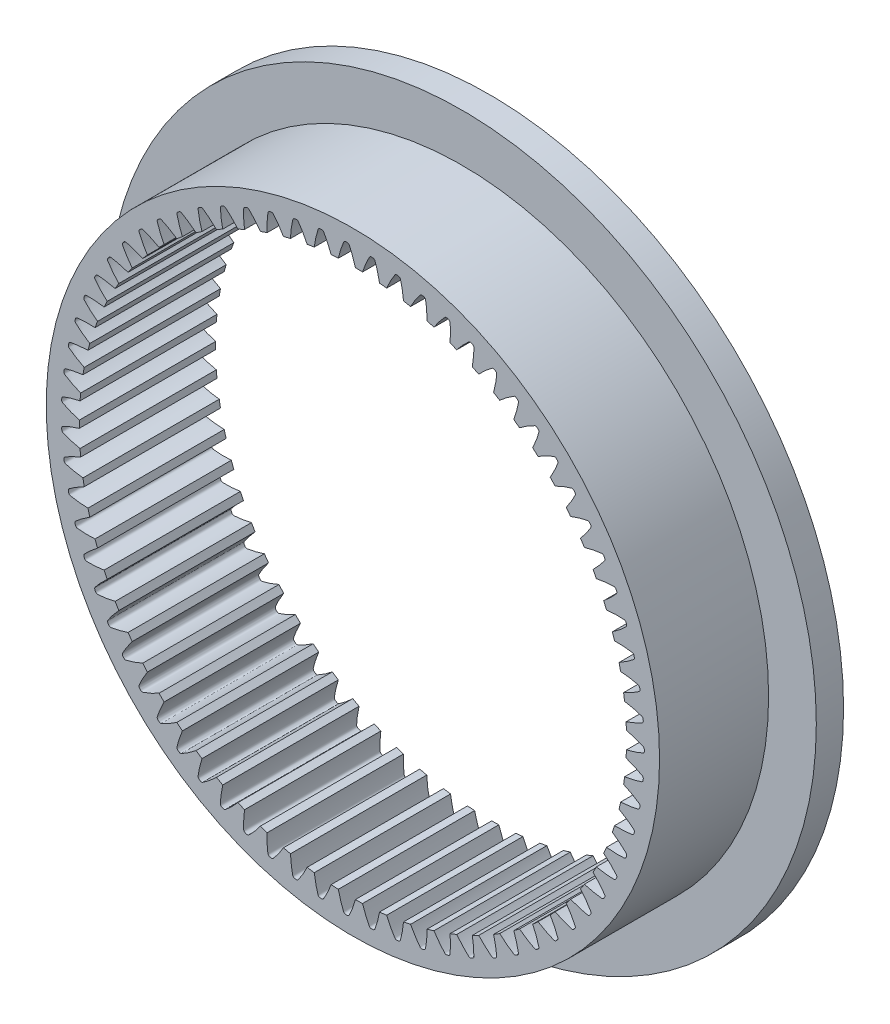
SolidWorks part; units mm, degrees
ref_plane "Front Plane" through (0, 0, 0) normal (0, 0, 1) x (1, 0, 0)
ref_plane "Top Plane" through (0, 0, 0) normal (0, 1, 0) x (1, 0, 0)
ref_plane "Right Plane" through (0, 0, 0) normal (1, 0, 0) x (0, 0, -1)
ref_axis "Axis1" through (0, 0, 55) along (0, 0, -1)
sketch "SketchRevolveRing_Gear_Follower02" plane through (0, 0, 0) normal (1, 0, 0) x (0, 0, -1)
  line L0 (0, 0) -> (25.4, 0) construction
  line L1 (-6.35, 25.4945) -> (-6.35, 38.1)
  line L2 (-6.35, 38.1) -> (6.35, 38.1)
  line L3 (6.35, 38.1) -> (6.35, 25.4945)
  line L4 (6.35, 25.4945) -> (-6.35, 25.4945)
  dimension "Side1" = 6.35
  dimension "OutsideRadius" = 38.1
  dimension "Side2" = 6.35
  dimension "MinorDiameter" = 25.4945
revolve "Ring_Gear_Follower02" add sketch "SketchRevolveRing_Gear_Follower02" angle 360 about L0
sketch "SketchToothRing_Gear_Follower02" plane through (0, 0, 0) normal (0, 0, 1) x (1, 0, 0)
  arc A0 (25.3229, -0.8287) -> (25.3229, 0.8287) centre (0, 0) ccw
  spline S0 degree 3 poles (25.3229, 0.8287) (25.4112, 0.8108) (25.5484, 0.7796) (25.737, 0.7307) (25.8937, 0.6865) (26.06, 0.6358) (26.2357, 0.5781) (26.4206, 0.513) (26.6146, 0.4404) (26.8165, 0.3579) (26.9656, 0.2993) (27.0537, 0.2557) (27.0798, 0.2362) (27.1027, 0.2137) (27.1221, 0.1881) (27.1375, 0.1599) (27.1526, 0.1203) (27.1579, 0.0772) (27.157, 0.0338) (27.1573, 0) (27.157, -0.0338) (27.1579, -0.0772) (27.1526, -0.1203) (27.1375, -0.1599) (27.1221, -0.1881) (27.1027, -0.2137) (27.0798, -0.2362) (27.0537, -0.2557) (26.9656, -0.2993) (26.8165, -0.3579) (26.6146, -0.4404) (26.4206, -0.513) (26.2357, -0.5781) (26.06, -0.6358) (25.8937, -0.6865) (25.737, -0.7307) (25.5484, -0.7796) (25.4112, -0.8108) (25.3229, -0.8287) knots 0 0 0 0 0.063805 0.09963 0.13807 0.179124 0.222794 0.269078 0.317977 0.369491 0.42362 0.431438 0.438996 0.446554 0.454113 0.461671 0.469229 0.484048 0.492024 0.5 0.507976 0.515952 0.530771 0.538329 0.545887 0.553446 0.561004 0.568562 0.57638 0.630509 0.682023 0.730922 0.777206 0.820876 0.86193 0.90037 0.936195 1 1 1 1
extrude "ToothExtrudeCutRing_Gear_Follower02" cut sketch "SketchToothRing_Gear_Follower02" against normal blind 6.35 and the other way blind 6.35
ref_axis "Axis2" through (41.91, 0, 0) along (-1, 0, 0)
ref_plane "Plane1" through (0, 0, 0) normal (0, 0, -1) x (1, 0, 0)
pattern_circular "PatternRing_Gear_Follower02" count 71 every 5.07 about axis through (0, 0, 55) along (0, 0, -1) of "ToothExtrudeCutRing_Gear_Follower02"
sketch "AuxiliarySketchRing_Gear_Follower02" plane through (0, 0, 0) normal (0, 0, 1) x (1, 0, 0)
  circle A0 centre (0, 0) radius 26.2335 construction
  circle A1 centre (0, 0) radius 24.6514 construction
  circle A2 centre (0, 0) radius 27.1572 construction
  circle A3 centre (0, 0) radius 25.4945 construction
  dimension "PitchDiameter" = 52.467
  dimension "BaseDiameter" = 49.3028
  dimension "MajorDiameter" = 54.3144
  dimension "MinorDiameter" = 50.989
sketch "Sketch1" plane through (0, 0, 6.35) normal (0, 0, 1) x (1, 0, 0)
  circle A0 centre (0, 0) radius 28.575
  circle A1 centre (0, 0) radius 38.1
  dimension "D1" = 57.15
  dimension "D2" = 76.2
extrude "Cut-Extrude1" cut sketch "Sketch1" against normal blind 10.16
sketch "Sketch2" plane through (0, 0, -3.81) normal (0, 0, 1) x (1, 0, 0)
  circle A0 centre (0, 0) radius 33.02
  circle A1 centre (0, 0) radius 38.1
  dimension "D1" = 66.04
  dimension "D2" = 76.2
extrude "Cut-Extrude2" cut sketch "Sketch2" against normal through all
